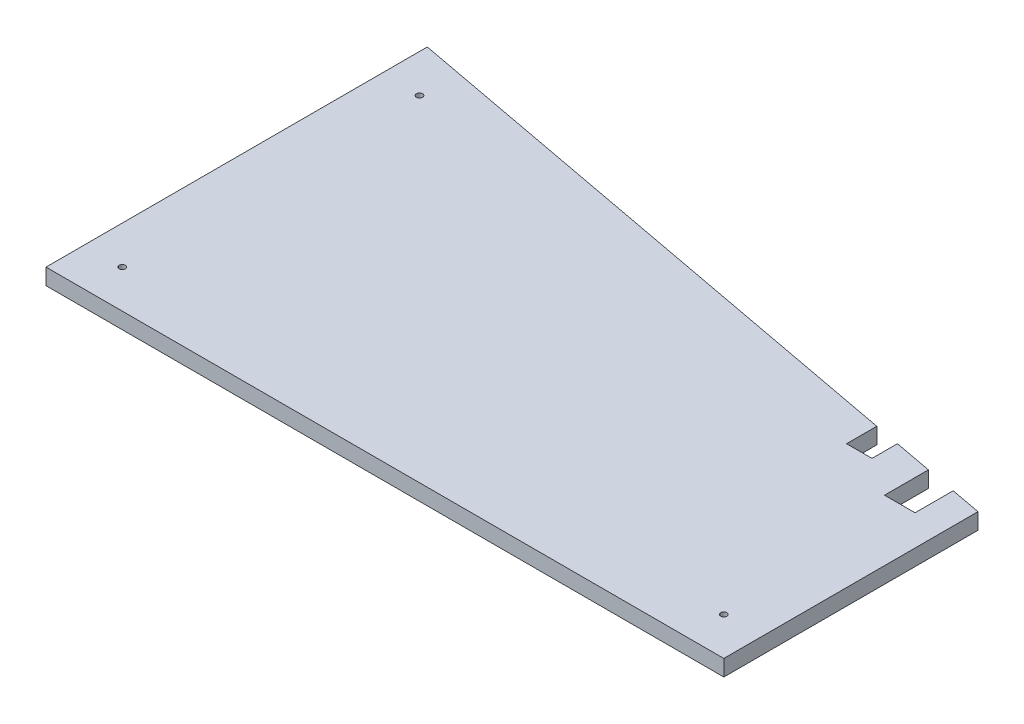
SolidWorks part; units mm, degrees
material "Balsa"
ref_plane "Front Plane" through (0, 0, 0) normal (0, 0, 1) x (1, 0, 0)
ref_plane "Top Plane" through (0, 0, 0) normal (0, 1, 0) x (1, 0, 0)
ref_plane "Right Plane" through (0, 0, 0) normal (1, 0, 0) x (0, 0, -1)
sketch "Sketch2" plane through (0, 0, 0) normal (0, 1, 0) x (1, 0, 0)
  line L0 (0, 0) -> (266.65, 0)
  line L1 (266.65, 0) -> (266.65, 100)
  line L2 (266.65, 100) -> (254.65, 102.2501)
  line L4 (242.6501, 104.5003) -> (242.6501, 87.2152)
  line L5 (242.6501, 87.2152) -> (254.65, 87.2501)
  line L6 (254.65, 87.2501) -> (254.65, 102.2501)
  line L7 (242.6501, 104.5003) -> (227.6501, 107.3129)
  line L8 (227.6501, 97.3129) -> (217.6501, 97.2838)
  line L9 (217.6501, 97.2838) -> (217.6501, 109.1881)
  line L10 (227.6501, 97.3129) -> (227.6501, 107.3129)
  line L11 (217.6501, 109.1881) -> (0, 150)
  line L16 (0, 150) -> (0, 0)
  point P10 (0, 0)
  point P12 (0, 0)
  point P15 (0, 0)
  dimension "D1" = 150
  dimension "D2" = 100
  dimension "D3" = 266.65
  dimension "D4" = 12
  dimension "D5" = 12
  dimension "D6" = 15
  dimension "D7" = 10
  dimension "D8" = 10
  dimension "D9" = 15
  dimension "D10" = 11.9042
  dimension "D11" = 17.2851
extrude "Boss-Extrude1" add sketch "Sketch2" along normal blind 6.35
sketch "Sketch3" plane through (0, 6.35, 0) normal (0, 1, 0) x (1, 0, 0)
  line L0 (0, 0) -> (266.65, 0) construction
  line L1 (0, 150) -> (0, 0) construction
  line L3 (217.6501, 109.1881) -> (0, 150) construction
  line L4 (266.65, 0) -> (266.65, 100) construction
  circle A0 centre (15, 131.9259) radius 1.225
  circle A1 centre (15, 15) radius 1.225
  circle A2 centre (251.65, 15) radius 1.225
  point P6 (0, 0)
  point P13 (15.4839, 147.0966)
  dimension "D1" = 2.45
  dimension "D2" = 2.45
  dimension "D3" = 2.45
  dimension "D4" = 15
  dimension "D5" = 15
  dimension "D6" = 15
  dimension "D7" = 15
  dimension "D8" = 15
  dimension "D9" = 15
extrude "Cut-Extrude1" cut sketch "Sketch3" against normal through all
